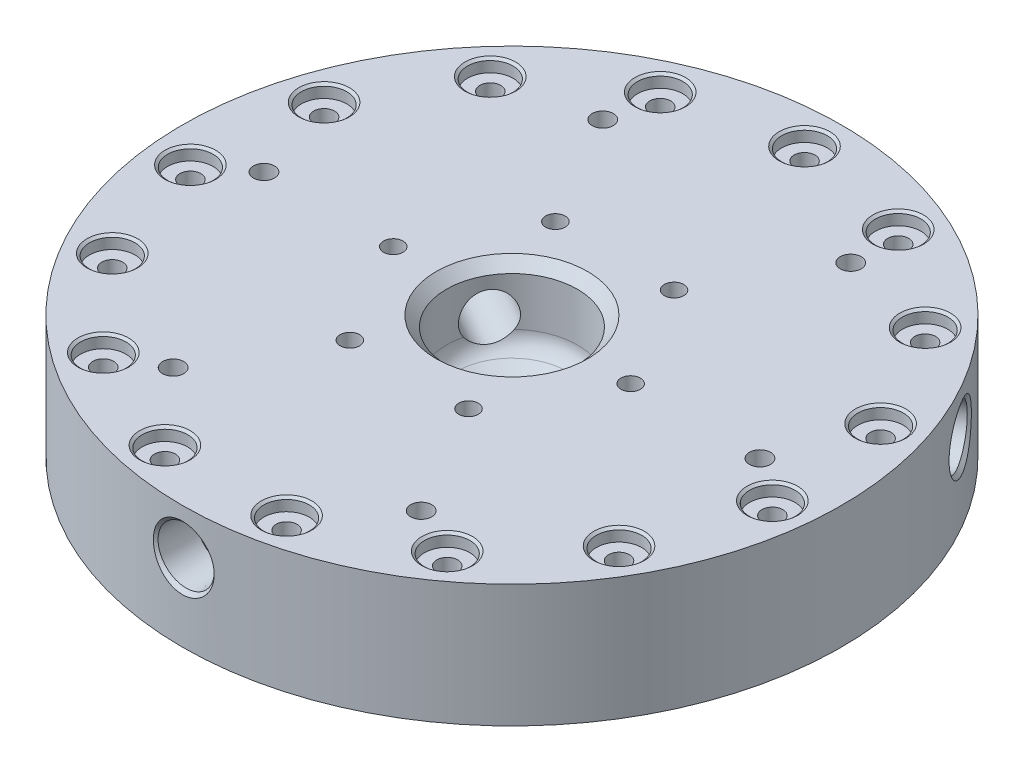
SolidWorks part; units mm, degrees
ref_plane "Front Plane" through (0, 0, 0) normal (0, 0, 1) x (1, 0, 0)
ref_plane "Top Plane" through (0, 0, 0) normal (0, 1, 0) x (1, 0, 0)
ref_plane "Right Plane" through (0, 0, 0) normal (1, 0, 0) x (0, 0, -1)
sketch "Sketch1" plane through (0, 0, 0) normal (0, 1, 0) x (1, 0, 0)
  circle A0 centre (0, 0) radius 80.54
  dimension "D1" = 161.08
extrude "Boss-Extrude1" add sketch "Sketch1" along normal blind 30
sketch "Sketch2" plane through (0, 0, 0) normal (0, 0, 1) x (1, 0, 0)
  line L0 (-5.9533, 0) -> (-5.9532, 4.1132)
  line L1 (-8.4533, 8.4434) -> (-13.5, 11.3571)
  line L2 (-16, 15.6872) -> (-16, 30)
  line L3 (80.54, 30) -> (-80.54, 30) construction
  line L4 (-16, 30) -> (0, 30)
  line L5 (0, 30) -> (0, 0)
  line L6 (0, 0) -> (-5.9533, 0)
  line L7 (-80.54, 0) -> (80.54, 0) construction
  arc A0 (-13.5, 11.3571) -> (-16, 15.6872) centre (-11, 15.6872) cw
  arc A1 (-5.9532, 4.1132) -> (-8.4533, 8.4434) centre (-10.9533, 4.1132) ccw
  point P15 (-5.9533, 7)
  dimension "D5" = 5
  dimension "D1" = 5.9533
  dimension "D2" = 7
  dimension "D3" = 16
  dimension "D4" = 30
revolve "Cut-Revolve1" cut sketch "Sketch2" angle 360 about L5
ref_plane "Plane1" through (0, 0, 80.54) normal (0, 0, 1) x (1, 0, 0)
hole_wizard "1/4 NPT Tapped Hole1" positions "Sketch4" profile "Sketch5" size "1/4" standard "ANSI Inch"
sketch "Sketch4" plane through (0, 0, 80.54) normal (0, 0, 1) x (1, 0, 0)
  point P0 (0, 18.9048)
sketch "Sketch5" plane through (0, 18.9048, 80.54) normal (1, 0, 0) x (0, -1, 0)
  line L0 (0, 0) -> (0, 83.8823)
  line L1 (5.5626, 80.54) -> (0, 83.8823)
  line L2 (-5.5626, 80.54) -> (0, 83.8823) construction
  line L3 (5.5626, 80.54) -> (5.5626, 10.02)
  line L4 (5.5626, 10.02) -> (6.5855, 10.02)
  line L5 (6.5855, 10.02) -> (6.858, 0.9208)
  line L6 (6.858, 0.9208) -> (7.7788, 0)
  line L7 (7.7788, 0) -> (0, 0)
  line L8 (0, -6.35) -> (0, 107.95) construction
  line L9 (-6.858, 0.9208) -> (-7.7788, 0) construction
  line L11 (-5.5626, 10.02) -> (-6.5855, 10.02) construction
  line L12 (-6.5855, 10.02) -> (-6.858, 0.9208) construction
  dimension "Tap Drill Dia." = 11.1252
  dimension "Tap Drill Depth" = 80.54
  dimension "Thread Dia." = 13.716
  dimension "Thread Angle" = 3.43
  dimension "Thread Depth" = 10.02
  dimension "C'Sink Dia." = 15.5575
  dimension "C'Sink Angle" = 90
  dimension "Drill Angle" = 118
pattern_circular "CirPattern1" count 3 over 360 about axis through (0, 30, 0) along (0, -1, 0) of "1/4 NPT Tapped Hole1"
hole_wizard "CBORE for #10 Binding Head Machine Screw1" positions "Sketch6" profile "Sketch7" counterbore size "#10" standard "ANSI Inch" end condition through all
sketch "Sketch6" plane through (0, 30, 0) normal (0, 1, 0) x (1, 0, 0)
  point P0 (0, 71.5)
  dimension "D1" = 71.5
sketch "Sketch7" plane through (0, 30, -71.5) normal (1, 0, 0) x (0, 0, 1)
  line L0 (0, 0) -> (0, 30)
  line L1 (0, 30) -> (2.5527, 30)
  line L3 (2.5527, 30) -> (2.5527, 3.1242)
  line L4 (5.5562, 3.1242) -> (2.5527, 3.1242)
  line L5 (5.5562, 3.1242) -> (5.5562, 0.5328)
  line L6 (5.5562, 0.5328) -> (6.1913, 0)
  line L7 (6.1913, 0) -> (0, 0)
  line L8 (-5.5562, 0.5328) -> (-6.1913, 0) construction
  line L11 (0, -6.35) -> (0, 107.95) construction
  dimension "Thru Hole Dia." = 5.1054
  dimension "Thru Hole Depth" = 30
  dimension "C'Bore Dia." = 11.1125
  dimension "C'Bore Depth" = 3.1242
  dimension "Near C'Sink Dia." = 12.3825
  dimension "Near C'Sink Angle" = 100
pattern_circular "CirPattern2" count 15 over 360 about axis through (0, 30, 0) along (0, -1, 0) of "CBORE for #10 Binding Head Machine Screw1"
sketch "Sketch12" plane through (0, 30, 0) normal (0, 1, 0) x (1, 0, 0)
  line L0 (0, 0) -> (0, 60.61)
  line L1 (0, 0) -> (30.305, 52.4898)
  circle A0 centre (0, 0) radius 60.61
  dimension "D1" = 121.22
  dimension "D2" = 30
hole_wizard "13/64 (0.20313) Diameter Hole3" positions "Sketch17" profile "Sketch19" hole size "13/64" standard "ANSI Inch"
sketch "Sketch17" plane through (0, 30, 0) normal (0, 1, 0) x (1, 0, 0)
  point P0 (30.305, 52.4898)
sketch "Sketch19" plane through (30.305, 30, -52.4898) normal (1, 0, 0) x (0, 0, 1)
  line L0 (0, 0) -> (0, 14.2501)
  line L1 (0, 14.2501) -> (2.5798, 12.7)
  line L2 (2.5798, 12.7) -> (2.5798, 0)
  line L5 (2.5798, 0) -> (0, 0)
  line L10 (0, 14.2501) -> (-2.5798, 12.7) construction
  line L11 (0, -6.35) -> (0, 107.95) construction
  dimension "Hole Dia." = 5.1595
  dimension "Hole Depth" = 12.7
  dimension "Drill Angle" = 118
pattern_circular "CirPattern3" count 6 over 360 about axis through (0, 30, 0) along (0, -1, 0) of "13/64 (0.20313) Diameter Hole3" reverse direction yes
sketch "Sketch20" plane through (0, 0, 0) normal (0, -1, 0) x (-1, 0, 0)
  circle A0 centre (0, 0) radius 55.14
  dimension "D1" = 110.28
sketch "Sketch21" plane through (0, 0, 0) normal (0, 0, 1) x (1, 0, 0)
  line L0 (-80.54, 0) -> (80.54, 0) construction
  line L1 (60, 0) -> (65, 0)
  line L2 (60, 0) -> (60, 3)
  line L3 (60, 3) -> (65, 3)
  line L4 (65, 0) -> (65, 3)
  line L5 (0, 0) -> (0, -8.9782) construction
  dimension "D1" = 60
  dimension "D2" = 5
  dimension "D3" = 3
revolve "Cut-Revolve2" cut sketch "Sketch21" angle 360 about L5
chamfer "Chamfer1" distance 2.5 angle 45 1 edges at (-16, 30, 0)
hole_wizard "3/16 (0.1875) Diameter Hole1" positions "Sketch27" profile "Sketch28" hole size "3/16" standard "ANSI Inch"
sketch "Sketch27" plane through (0, 30, 0) normal (0, 1, 0) x (1, 0, 0)
  point P0 (29, 0)
  dimension "D1" = 29
sketch "Sketch28" plane through (29, 30, 0) normal (1, 0, 0) x (0, 0, 1)
  line L0 (0, 0) -> (0, 13.4308)
  line L1 (0, 13.4308) -> (2.3812, 12)
  line L2 (2.3812, 12) -> (2.3812, 0)
  line L5 (2.3812, 0) -> (0, 0)
  line L10 (0, 13.4308) -> (-2.3813, 12) construction
  line L11 (0, -6.35) -> (0, 107.95) construction
  dimension "Hole Dia." = 4.7625
  dimension "Hole Depth" = 12
  dimension "Drill Angle" = 118
pattern_circular "CirPattern4" count 6 over 360 about axis through (0, 30, 0) along (0, -1, 0) of "3/16 (0.1875) Diameter Hole1" reverse direction yes
